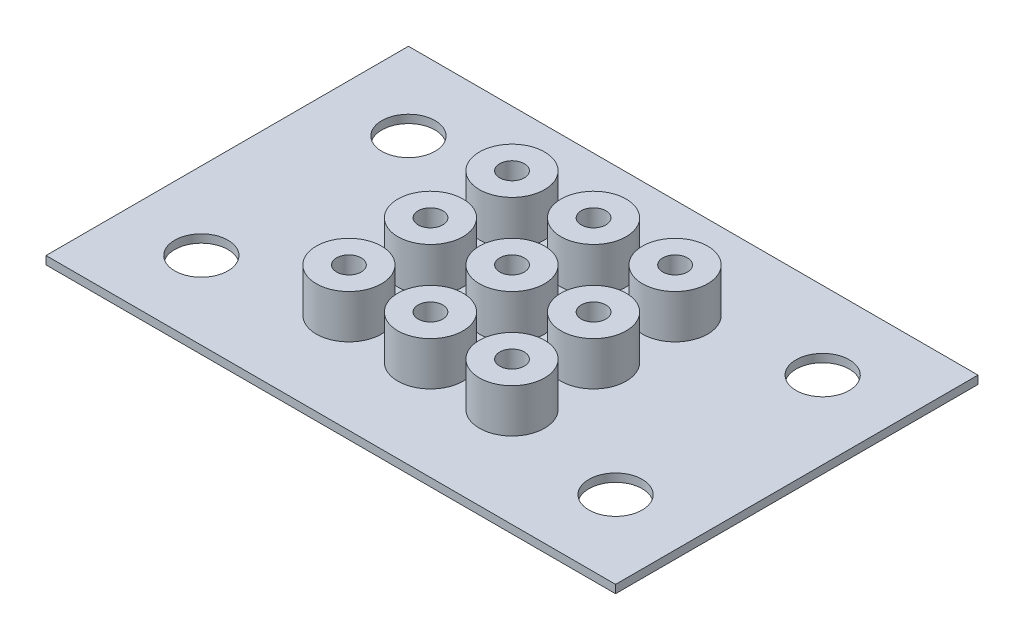
SolidWorks part; units mm, degrees
ref_plane "Front Plane" through (0, 0, 0) normal (0, 0, 1) x (1, 0, 0)
ref_plane "Top Plane" through (0, 0, 0) normal (0, 1, 0) x (1, 0, 0)
ref_plane "Right Plane" through (0, 0, 0) normal (1, 0, 0) x (0, 0, -1)
sketch "Sketch1" plane through (0, 0, 0) normal (0, 1, 0) x (1, 0, 0)
  line L0 (9.525, 34.925) -> (0, 34.925) construction
  line L1 (0, 0) -> (69.85, 0)
  line L2 (0, 0) -> (0, 44.45)
  line L3 (0, 44.45) -> (69.85, 44.45)
  line L4 (69.85, 0) -> (69.85, 44.45)
  line L5 (9.525, 34.925) -> (60.325, 34.925) construction
  line L6 (9.525, 34.925) -> (9.525, 9.525) construction
  line L7 (9.525, 9.525) -> (60.325, 9.525) construction
  line L8 (60.325, 34.925) -> (60.325, 9.525) construction
  line L9 (9.525, 34.925) -> (9.525, 44.45) construction
  line L10 (34.925, 22.225) -> (34.925, 32.225) construction
  circle A0 centre (9.525, 34.925) radius 3.2639
  circle A1 centre (60.325, 34.925) radius 3.2639
  circle A2 centre (9.525, 9.525) radius 3.2639
  circle A3 centre (60.325, 9.525) radius 3.2639
  circle A4 centre (34.925, 22.225) radius 1.25
  circle A5 centre (44.925, 22.225) radius 1.25
  circle A6 centre (44.925, 32.225) radius 1.25
  circle A7 centre (34.925, 32.225) radius 1.25
  circle A8 centre (24.925, 22.225) radius 1.25
  circle A9 centre (24.925, 32.225) radius 1.25
  circle A10 centre (34.925, 32.225) radius 1.25
  circle A11 centre (44.925, 22.225) radius 1.25
  circle A12 centre (44.925, 12.225) radius 1.25
  circle A13 centre (34.925, 12.225) radius 1.25
  circle A14 centre (24.925, 22.225) radius 1.25
  circle A15 centre (24.925, 12.225) radius 1.25
  circle A16 centre (34.925, 12.225) radius 1.25
  point P13 (34.925, 34.925)
  point P14 (34.925, 44.45)
  point P20 (69.85, 22.225)
  dimension "D5" = 6.5278
  dimension "D6" = 2.5
  dimension "D1" = 69.85
  dimension "D2" = 44.45
  dimension "D3" = 50.8
  dimension "D4" = 25.4
  dimension "D9" = 10
  dimension "D16" = 10
  dimension "D17" = 10
  dimension "D18" = 10
  dimension "D19" = 10
  dimension "D20" = 10
  dimension "D21" = 10
  dimension "D22" = 10
  dimension "D7" = 2
  dimension "D8" = 2
  dimension "D10" = 2
  dimension "D11" = 2
  dimension "D12" = 2
  dimension "D13" = 2
  dimension "D14" = 2
  dimension "D15" = 2
extrude "Boss-Extrude1" add sketch "Sketch1" along normal blind 1 contours L1 L4 L3 L2 A15 A13 A12 A9 A8 A7 A6 A5 A4 A3 A2 A1 A0 region at (0.8279, 0, -22.225)
sketch "Sketch2" plane through (0, 1, 0) normal (0, 1, 0) x (1, 0, 0)
  line L0 (34.925, 22.225) -> (34.925, 32.225) construction
  circle A0 centre (34.925, 22.225) radius 4
  circle A1 centre (34.925, 22.225) radius 1.51
  circle A2 centre (44.925, 22.225) radius 4
  circle A3 centre (44.925, 22.225) radius 1.51
  circle A4 centre (44.925, 32.225) radius 4
  circle A5 centre (44.925, 32.225) radius 1.51
  circle A6 centre (34.925, 32.225) radius 4
  circle A7 centre (34.925, 32.225) radius 1.51
  circle A8 centre (44.925, 22.225) radius 1.51
  circle A9 centre (44.925, 22.225) radius 4
  circle A10 centre (44.925, 12.225) radius 1.51
  circle A11 centre (44.925, 12.225) radius 4
  circle A12 centre (34.925, 12.225) radius 1.51
  circle A13 centre (34.925, 12.225) radius 4
  circle A14 centre (24.925, 22.225) radius 4
  circle A15 centre (24.925, 22.225) radius 1.51
  circle A16 centre (24.925, 32.225) radius 4
  circle A17 centre (24.925, 32.225) radius 1.51
  circle A18 centre (34.925, 32.225) radius 4
  circle A19 centre (34.925, 32.225) radius 1.51
  circle A20 centre (24.925, 22.225) radius 1.51
  circle A21 centre (24.925, 22.225) radius 4
  circle A22 centre (24.925, 12.225) radius 1.51
  circle A23 centre (24.925, 12.225) radius 4
  circle A24 centre (34.925, 12.225) radius 1.51
  circle A25 centre (34.925, 12.225) radius 4
  point P26 (23.5196, 21.6929)
  dimension "D1" = 3.02
  dimension "D2" = 8
  dimension "D5" = 10
  dimension "D10" = 10
  dimension "D11" = 10
  dimension "D12" = 10
  dimension "D13" = 10
  dimension "D14" = 10
  dimension "D15" = 10
  dimension "D16" = 10
  dimension "D3" = 2
  dimension "D4" = 2
  dimension "D6" = 2
  dimension "D7" = 2
  dimension "D8" = 2
  dimension "D9" = 2
extrude "Boss-Extrude2" add sketch "Sketch2" along normal blind 5.35 contours A16 A17 | A14 A15 | A6 A7 | A4 A5 | A2 A3 | A1 A0 | A23 A22 | A13 A12 | A11 A10 region at (31.0381, 1, -22.225) region at (41.0381, 1, -22.225) region at (41.0381, 1, -32.225) region at (31.0381, 1, -32.225) region at (41.0381, 1, -12.225) region at (31.0381, 1, -12.225) region at (21.0381, 1, -22.225) region at (21.0381, 1, -32.225) region at (21.0381, 1, -12.225)
